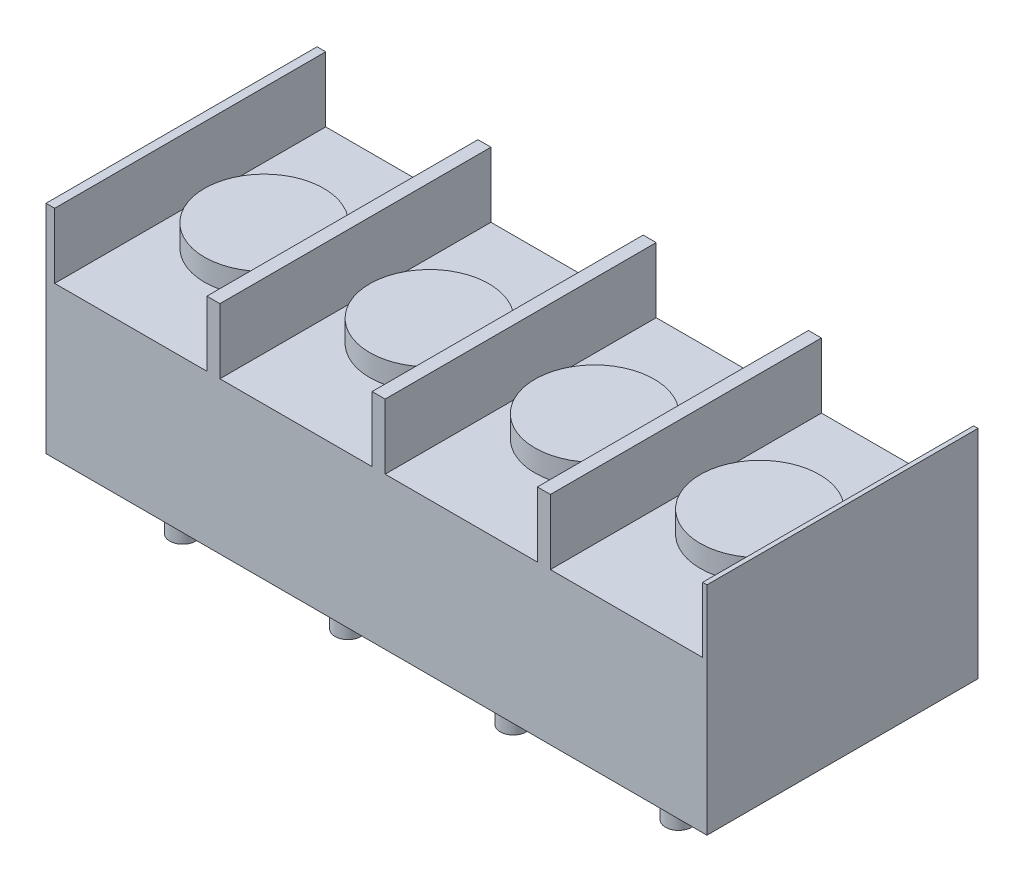
SolidWorks part; units mm, degrees
ref_plane "前视基准面" through (0, 0, 0) normal (0, 0, 1) x (1, 0, 0)
ref_plane "上视基准面" through (0, 0, 0) normal (0, 1, 0) x (1, 0, 0)
ref_plane "右视基准面" through (0, 0, 0) normal (1, 0, 0) x (0, 0, -1)
sketch "草图1" plane through (0, 0, 0) normal (0, 1, 0) x (1, 0, 0)
  line L0 (-11.1447, 0) -> (12.1543, 0) construction
  line L1 (-15.24, 6.25) -> (15.24, 6.25)
  line L2 (-15.24, 6.25) -> (-15.24, -6.25)
  line L3 (-15.24, -6.25) -> (15.24, -6.25)
  line L4 (15.24, 6.25) -> (15.24, -6.25)
  line L5 (0, 11.4931) -> (0, -8.9219) construction
  dimension "D1" = 30.48
  dimension "D2" = 12.5
extrude "拉伸1" add sketch "草图1" along normal blind 10
sketch "草图2" plane through (0, 10, 0) normal (0, 1, 0) x (-1, 0, 0)
  line L0 (7.22, -6.25) -> (0.2, -6.25)
  line L1 (7.22, -6.25) -> (7.22, 6.25)
  line L2 (-15.24, -6.25) -> (15.24, -6.25) construction
  line L3 (14.84, -6.25) -> (7.82, -6.25)
  line L4 (14.84, -6.25) -> (14.84, 6.25)
  line L5 (14.84, 6.25) -> (7.82, 6.25)
  line L6 (7.22, 6.25) -> (0.2, 6.25)
  line L7 (7.82, -6.25) -> (7.82, 6.25)
  line L8 (15.24, 6.25) -> (-15.24, 6.25) construction
  line L9 (15.24, -6.25) -> (15.24, 6.25) construction
  line L10 (0.2, -6.25) -> (0.2, 6.25)
  line L11 (-0.4, -6.25) -> (-7.42, -6.25)
  line L12 (-0.4, -6.25) -> (-0.4, 6.25)
  line L13 (-0.4, 6.25) -> (-7.42, 6.25)
  line L14 (-7.42, -6.25) -> (-7.42, 6.25)
  line L15 (-8.02, -6.25) -> (-15.04, -6.25)
  line L16 (-8.02, -6.25) -> (-8.02, 6.25)
  line L17 (-8.02, 6.25) -> (-15.04, 6.25)
  line L18 (-15.04, -6.25) -> (-15.04, 6.25)
  dimension "D1" = 7.02
  dimension "D2" = 0.4
  dimension "D3" = 4
extrude "切除-拉伸1" cut sketch "草图2" against normal blind 3
sketch "草图3" plane through (0, 0, 0) normal (0, -1, 0) x (1, 0, 0)
  line L0 (9.9189, 3.75) -> (-9.4712, 3.75) construction
  line L1 (0, -8.128) -> (0, 7.9902) construction
  circle A0 centre (3.81, 3.75) radius 0.6
  circle A1 centre (11.43, 3.75) radius 0.6
  circle A2 centre (-3.81, 3.75) radius 0.6
  circle A3 centre (-11.43, 3.75) radius 0.6
  dimension "D2" = 1.2
  dimension "D1" = 10
  dimension "D3" = 3.81
  dimension "D4" = 2
  dimension "D5" = 3
extrude "拉伸2" add sketch "草图3" along normal blind 2.54
sketch "草图4" plane through (0, 7, 0) normal (0, 1, 0) x (-1, 0, 0)
  line L0 (-9.5136, 0) -> (8.6579, 0) construction
  line L1 (0, -7.7686) -> (0, 8.3952) construction
  circle A0 centre (-3.81, 0) radius 2.75
  circle A1 centre (3.81, 0) radius 2.75
  circle A2 centre (11.43, 0) radius 2.75
  circle A3 centre (-11.43, 0) radius 2.75
  dimension "D1" = 5.5
  dimension "D3" = 3
  dimension "D2" = 3.81
  dimension "D4" = 2
extrude "拉伸3" add sketch "草图4" along normal blind 1
